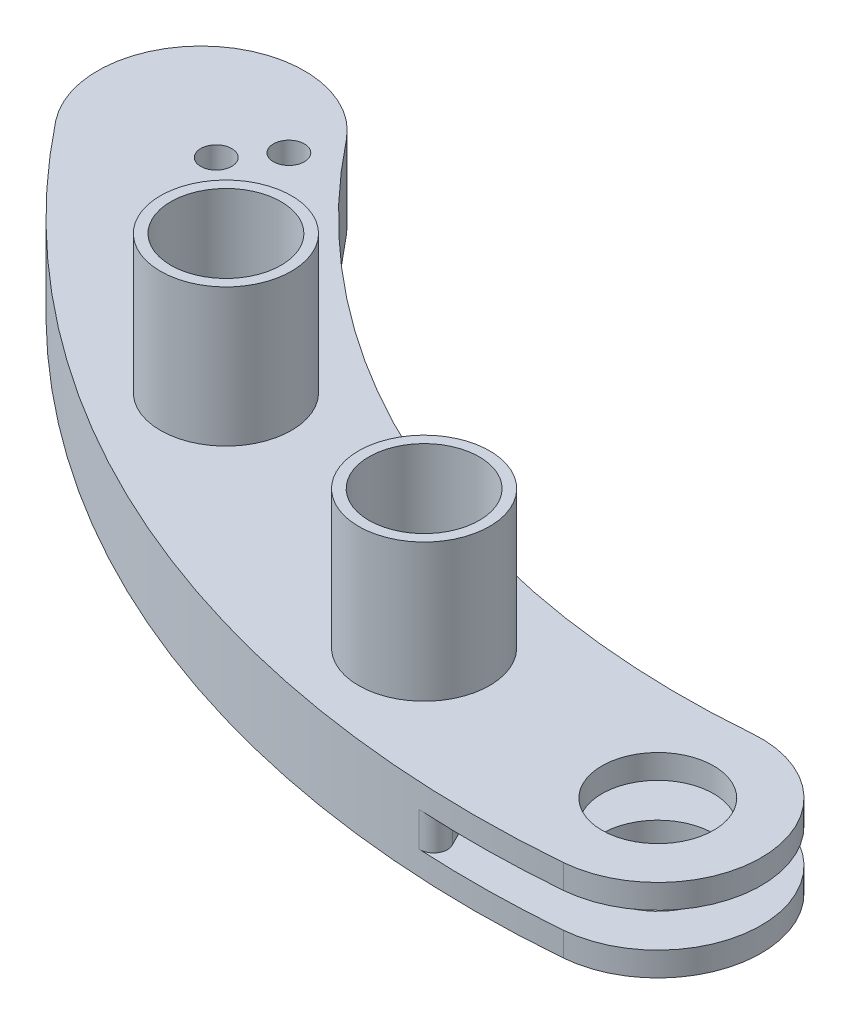
SolidWorks part; units mm, degrees
ref_plane "Front Plane" through (0, 0, 0) normal (0, 0, 1) x (1, 0, 0)
ref_plane "Top Plane" through (0, 0, 0) normal (0, 1, 0) x (1, 0, 0)
ref_plane "Right Plane" through (0, 0, 0) normal (1, 0, 0) x (0, 0, -1)
sketch "Sketch1" plane through (0, 0, 0) normal (0, 1, 0) x (1, 0, 0)
  arc A0 (0, 0) -> (-117, 50.7404) centre (-11.1561, 134.5383) cw construction
  arc A1 (-128.7604, 41.4296) -> (1.2396, -14.9487) centre (-11.1561, 134.5383) ccw
  arc A2 (-105.2396, 60.0513) -> (-1.2396, 14.9487) centre (-11.1561, 134.5383) ccw
  arc A3 (-105.2396, 60.0513) -> (-128.7604, 41.4296) centre (-117, 50.7404) ccw
  arc A4 (1.2396, -14.9487) -> (-1.2396, 14.9487) centre (0, 0) ccw
  arc A5 (-16.6792, 14.6654) -> (-15.4249, -15.401) centre (4.9458, 0.5082) ccw
  point P3 (-64.8692, 10.6839)
  dimension "D3" = 30
  dimension "D4" = 150
  dimension "D1" = 75
  dimension "D2" = 130
extrude "Boss-Extrude4" add sketch "Sketch1" along normal blind 12 contours A5 A2 A3 A1 region at (-76.6272, 0, -21.3687)
extrude "Boss-Extrude5" add sketch "Sketch1<6>" along normal blind 3.5 contours A2 A5 A1 A4 region at (-3.6374, 0, 0.1249)
sketch "Sketch1<6>" plane through (0, 0, 0) normal (0, 1, 0) x (1, 0, 0) same geometry as "Sketch1"
extrude "Boss-Extrude6" add sketch "Sketch1<8>" along normal blind 12 contours A2 A5 A1 A4 region at (-3.6374, 0, 0.1249)
sketch "Sketch1<8>" plane through (0, 0, 0) normal (0, 1, 0) x (1, 0, 0) same geometry as "Sketch1"
extrude "Cut-Extrude2" cut sketch "Sketch1<9>" along normal blind 8.5 contours A2 A5 A1 A4 region at (-3.6374, 0, 0.1249)
sketch "Sketch1<9>" plane through (0, 0, 0) normal (0, 1, 0) x (1, 0, 0) same geometry as "Sketch1"
extrude "Boss-Extrude7" add sketch "Sketch1<10>" along normal blind 3.5 contours A2 A5 A1 A4 region at (-3.6374, 0, 0.1249)
sketch "Sketch1<10>" plane through (0, 0, 0) normal (0, 1, 0) x (1, 0, 0) same geometry as "Sketch1"
sketch "Sketch2" plane through (0, 12, 0) normal (0, 1, 0) x (1, 0, 0)
  circle A0 centre (0, 0) radius 8.1
  dimension "D1" = 16.2
extrude "Cut-Extrude3" cut sketch "Sketch2" against normal blind 12
fillet "Fillet1" radius 5 1 edges at (-16.6792, 6, -14.6654)
fillet "Fillet2" radius 2 1 edges at (-15.4249, 6, 15.401)
sketch "Sketch3" plane through (0, 12, 0) normal (0, 1, 0) x (1, 0, 0)
  circle A0 centre (-107.8166, 54.3025) radius 2.25
  circle A1 centre (-112.4991, 48.4438) radius 2.25
  point P4 (0, 0)
  dimension "D1" = 4.5
  dimension "D2" = 4.5
  dimension "D3" = 7.5
  dimension "D4" = 6.3
extrude "Cut-Extrude4" cut sketch "Sketch3" against normal blind 12
sketch "Sketch4" plane through (0, 12, 0) normal (0, 1, 0) x (1, 0, 0)
  circle A0 centre (-35.8241, 1.9278) radius 8
  circle A1 centre (-35.8241, 1.9278) radius 9.5
  circle A2 centre (-82.2472, 19.6043) radius 8
  circle A3 centre (-82.2472, 19.6043) radius 9.5
  dimension "D1" = 16
  dimension "D2" = 19
extrude "Boss-Extrude8" add sketch "Sketch4" along normal blind 20
